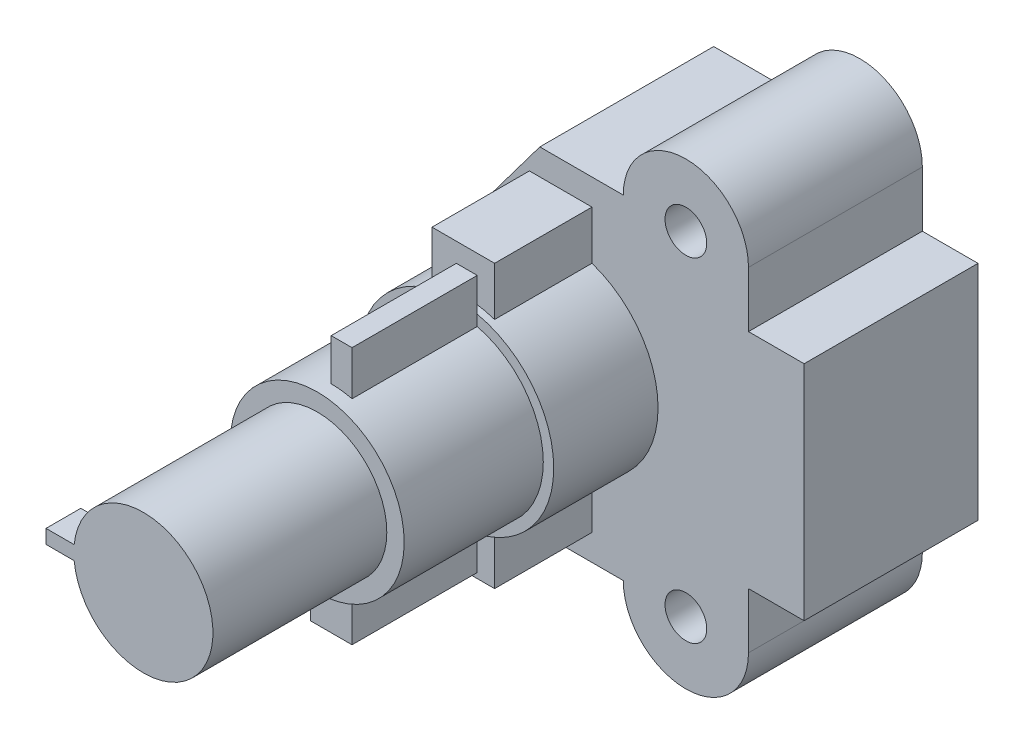
SolidWorks part; units mm, degrees
ref_plane "Front Plane" through (0, 0, 0) normal (1, 0, 0) x (0, 1, 0)
ref_plane "Top Plane" through (0, 0, 0) normal (0, 0, 1) x (0, 1, 0)
ref_plane "Right Plane" through (0, 0, 0) normal (0, 1, 0) x (-1, 0, 0)
sketch "Sketch1" plane through (0, 0, 0) normal (0, 0, 1) x (0, 1, 0)
  line L0 (24, 0) -> (-24, 0) construction
  line L1 (0, 0) -> (0, 18) construction
  line L2 (-24, -9) -> (24, -9)
  line L3 (0, -9) -> (0, -17) construction
  line L4 (16, -17) -> (-16, -17)
  line L5 (-16, -17) -> (-16, -9)
  line L6 (16, -17) -> (16, -9)
  line L7 (-24, 9) -> (-24, 21)
  line L8 (-24, 21) -> (-8, 33)
  line L9 (0, 18) -> (0, 33) construction
  line L10 (8, 33) -> (-8, 33)
  line L11 (24, 9) -> (24, 21)
  line L12 (24, 21) -> (8, 33)
  circle A0 centre (-24, 0) radius 3
  circle A1 centre (24, 0) radius 3
  circle A2 centre (-24, 0) radius 9
  circle A3 centre (24, 0) radius 9
  point P4 (0, 0)
  point P19 (0, -17)
  dimension "D1" = 6
  dimension "D3" = 18
  dimension "D2" = 48
  dimension "D6" = 8
  dimension "D7" = 32
  dimension "D8" = 15
  dimension "D9" = 12
  dimension "D10" = 20
  dimension "D4" = 6
  dimension "D5" = 6
extrude "Boss-Extrude1" add sketch "Sketch1" against normal blind 25 contours A2 A0 | A3 L11 L12 L10 L8 L7 A2 L2 | A3 A1 | L4 L6 L2 L5 region at (-11.866, 0, 0) region at (0, -32.7454, 0) region at (13, 0, 0) region at (0, 15.2546, 0)
sketch "Sketch2" plane through (0, 0, 0) normal (0, 0, 1) x (1, 0, 0)
  line L0 (-18, 14) -> (-18, 20.2571) construction
  line L1 (-13.5, 20.2571) -> (-22.5, 20.2571)
  line L2 (-22.5, 20.2571) -> (-22.5, 13.2571)
  line L3 (-13.5, 20.2571) -> (-13.5, 13.2571)
  line L4 (-18, 0) -> (-33, 0) construction
  line L5 (-18, 0) -> (-33, 0) construction
  line L6 (-13.5, -20.2571) -> (-22.5, -20.2571)
  line L7 (-13.5, -20.2571) -> (-13.5, -13.2571)
  line L8 (-22.5, -20.2571) -> (-22.5, -13.2571)
  arc A0 (-22.5, 13.2571) -> (-22.5, -13.2571) centre (-18, 0) ccw
  arc A1 (-22.5, 13.2571) -> (-13.5, 13.2571) centre (-18, 0) cw
  arc A3 (-22.5, -13.2571) -> (-13.5, -13.2571) centre (-18, 0) ccw
  arc A4 (-13.5, -13.2571) -> (-13.5, 13.2571) centre (-18, 0) ccw
  dimension "D1" = 28
  dimension "D2" = 7
  dimension "D3" = 9
extrude "Boss-Extrude2" add sketch "Sketch2" along normal blind 15 contours A3 A4 A1 A0 region at (-18, 0, 0)
extrude "Boss-Extrude3" add sketch "Sketch2<3>" along normal blind 14 contours A3 L8 L6 L7 | L2 A1 L3 L1 region at (-18, 17.0023, 0) region at (-18, -17.0023, 0)
sketch "Sketch2<3>" plane through (0, 0, 0) normal (0, 0, 1) x (1, 0, 0) same geometry as "Sketch2"
sketch "Sketch3" plane through (0, 0, 15) normal (0, 0, 1) x (1, 0, 0)
  line L0 (-18, 12.5) -> (-18, 18.5) construction
  line L1 (-15, 18.5) -> (-21, 18.5)
  line L2 (-21, 18.5) -> (-21, 12.1347)
  line L3 (-15, 18.5) -> (-15, 12.1347)
  line L4 (-18, 0) -> (-33, 0) construction
  line L5 (-18, 0) -> (-33, 0)
  line L6 (-15, -18.5) -> (-15, -12.1347)
  line L7 (-21, -18.5) -> (-21, -12.1347)
  line L8 (-15, -18.5) -> (-21, -18.5)
  circle A0 centre (-18, 0) radius 12.5
  point P8 (-18, 18.5)
  dimension "D1" = 25
  dimension "D2" = 6
  dimension "D3" = 6
extrude "Boss-Extrude4" add sketch "Sketch3" along normal blind 20 contours A0 region at (-8.4359, 7.4876, 15)
extrude "Boss-Extrude5" add sketch "Sketch3<3>" along normal blind 18 contours A0 L7 L6 | L8 L6 L7 | L0 L3 L1 | L0 A0 L3 region at (-16.4851, 15.4385, 15) region at (-18, -15.4385, 15)
sketch "Sketch3<3>" plane through (0, 0, 15) normal (0, 0, 1) x (1, 0, 0) same geometry as "Sketch3"
sketch "Sketch5" plane through (0, 0, 35) normal (0, 0, 1) x (1, 0, 0)
  circle A0 centre (-18, 0) radius 10
  dimension "D1" = 20
extrude "Boss-Extrude6" add sketch "Sketch5" along normal blind 25
sketch "Sketch6" plane through (0, 0, 60) normal (0, 0, 1) x (1, 0, 0)
  line L0 (-18, 0) -> (-29.5, 0) construction
  dimension "D1" = 11.5
ref_plane "Plane1" through (-28, 0, 60) normal (-1, 0, 0) x (0, 0, 1)
sketch "Sketch7" plane through (-28, 0, 60) normal (-1, 0, 0) x (0, 0, 1)
  line L0 (0, 0) -> (-5, 0) construction
  line L1 (0, -10) -> (0, 10) construction
  line L2 (-5, -3) -> (-5, 3)
  line L3 (-5, 3) -> (-8, 3)
  line L4 (-8, 3) -> (-8, -3)
  line L5 (-8, -3) -> (-5, -3)
  line L6 (0, -1) -> (0, 1)
  line L7 (0, 1) -> (-5, 1)
  line L8 (-5, 1) -> (-5, -1)
  line L9 (-5, -1) -> (0, -1)
  point P8 (-5, 0)
  point P13 (0, 0)
  dimension "D1" = 3
  dimension "D2" = 6
  dimension "D3" = 5
  dimension "D4" = 2
extrude "Boss-Extrude7" add sketch "Sketch7" against normal up to surface (0.4606 mm away) contours L4 L5 L2 L8 L3 | L0 L6 L7 L8 | L6 L0 L2 L9 region at (-28, -0.5, 57.5) region at (-28, 0.5, 57.5) region at (-28, 0, 53.5) up to face at (-8, 0, 60)
extrude "Boss-Extrude8" add sketch "Sketch7<2>" along normal blind 1 contours L4 L5 L2 L8 L3 region at (-28, 0, 53.5)
sketch "Sketch7<2>" plane through (-28, 0, 60) normal (-1, 0, 0) x (0, 0, 1) same geometry as "Sketch7"
extrude "Boss-Extrude9" add sketch "Sketch7<4>" along normal blind 4 contours L0 L6 L7 L8 | L6 L0 L2 L9 region at (-28, -0.5, 57.5) region at (-28, 0.5, 57.5)
sketch "Sketch7<4>" plane through (-28, 0, 60) normal (-1, 0, 0) x (0, 0, 1) same geometry as "Sketch7"
sketch "Sketch9" plane through (0, 0, 0) normal (0, 1, 0) x (-1, 0, 0)
  line L0 (17.9749, 60) -> (17.9749, 75) construction
  line L1 (27.9499, 60) -> (8, 60) construction
  dimension "D1" = 15
sketch "Sketch10" plane through (0, 0, -25) normal (0, 0, -1) x (1, 0, 0)
  circle A0 centre (0, 24) radius 8
  circle A1 centre (0, -24) radius 8
  arc A2 (9, 24) -> (-9, 24) centre (0, 24) ccw construction
  dimension "D1" = 1
extrude "Cut-Extrude1" cut sketch "Sketch10" against normal blind 15
